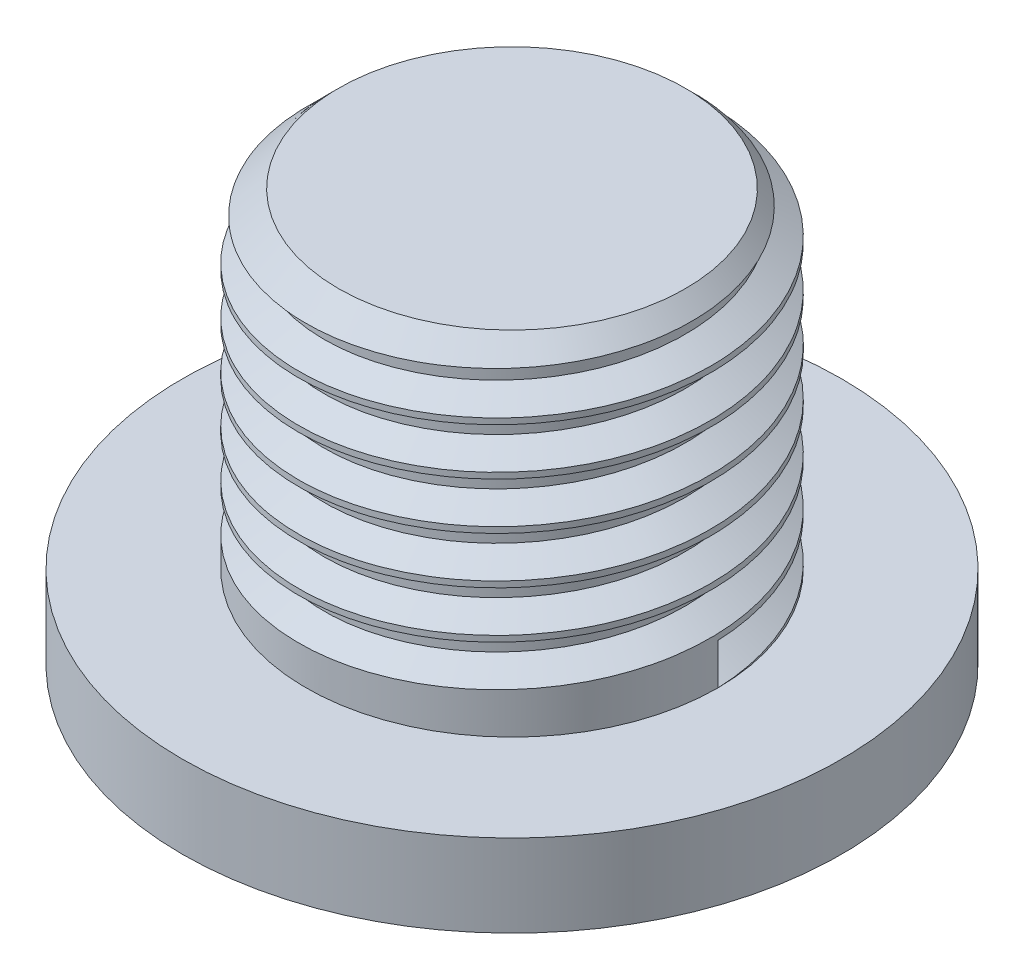
SolidWorks part; units mm, degrees
ref_plane "Front Plane" through (0, 0, 0) normal (0, 0, 1) x (1, 0, 0)
ref_plane "Top Plane" through (0, 0, 0) normal (0, 1, 0) x (1, 0, 0)
ref_plane "Right Plane" through (0, 0, 0) normal (1, 0, 0) x (0, 0, -1)
sketch "Sketch2" plane through (0, 0, 0) normal (0, 1, 0) x (1, 0, 0)
  circle A0 centre (0, 0) radius 25.4
  circle A1 centre (0, 0) radius 15.875
  dimension "D1" = 50.8
  dimension "D2" = 31.75
extrude "Boss-Extrude1" add sketch "Sketch2" along normal blind 25.4 contours A1 region at (0, 0, 0)
extrude "Boss-Extrude2" add sketch "Sketch2<3>" against normal blind 6.35 separate body contours A1 | A0 A1 region at (-24.6816, 0, 0) region at (0, 0, 0)
sketch "Sketch2<3>" plane through (0, 0, 0) normal (0, 1, 0) x (1, 0, 0) same geometry as "Sketch2"
sketch "Sketch4" plane through (0, -6.35, 0) normal (0, -1, 0) x (1, 0, 0)
  line L0 (0, -27.94) -> (0, 27.94) construction
  line L1 (0, -9.2376) -> (8, -4.6188)
  line L2 (8, -4.6188) -> (8, 4.6188)
  line L3 (8, 4.6188) -> (0, 9.2376)
  line L4 (0, 9.2376) -> (-8, 4.6188)
  line L5 (-8, 4.6188) -> (-8, -4.6188)
  line L6 (-8, -4.6188) -> (0, -9.2376)
  circle A0 centre (0, 0) radius 8 construction
  dimension "D1" = 16
extrude "Cut-Extrude2" cut sketch "Sketch4" against normal blind 7
chamfer "Chamfer1" distance 2.5 angle 45 1 edges at (0, 25.4, 15.875)
thread "Thread1" pitch 3.6286 method cut profile "Thread Profile1" start angle 0, offset 0, length 0, pitch 3.6286, diameter 31.75
ref_plane "Plane1" through (15.875, 0, 0) normal (0, 0, 1) x (1, 0, 0)
sketch "Thread Profile1" plane through (15.875, 0, 0) normal (0, 0, 1) x (1, 0, 0)
  line L0 (0, 0) -> (0, 3.6286) construction
  line L11 (0, 0) -> (0, 3.175)
  line L12 (0, 3.175) -> (-1.964, 2.0411)
  line L13 (-1.964, 2.0411) -> (-1.964, 1.1339)
  line L15 (-1.964, 1.1339) -> (0, 0)
  line L17 (-1.964, 1.5875) -> (0, 1.5875) construction
  point P2 (0, 0)
  dimension "Pitch" = 3.6286
  dimension "Profile_Angle" = 60
  dimension "Profile_Land" = 0.9071
  dimension "Profile_Height" = 1.964
